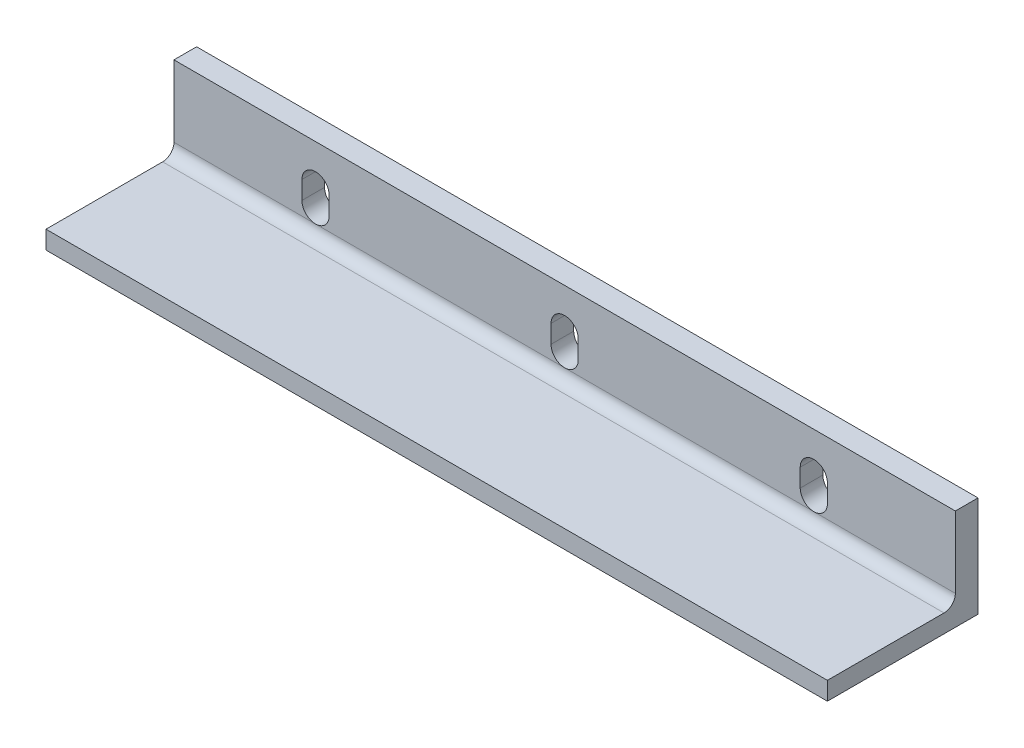
SolidWorks part; units mm, degrees
material "FR4_stuffedProtoboard"
ref_plane "Front Plane" through (0, 0, 0) normal (0, 0, 1) x (1, 0, 0)
ref_plane "Top Plane" through (0, 0, 0) normal (0, 1, 0) x (1, 0, 0)
ref_plane "Right Plane" through (0, 0, 0) normal (1, 0, 0) x (0, 0, -1)
sketch "Sketch1" plane through (0, 0, 0) normal (0, 1, 0) x (1, 0, 0)
  line L1 (-34.5, -6.65) -> (34.5, -6.65)
  line L2 (-34.5, -6.65) -> (-34.5, 6.65)
  line L3 (-34.5, 6.65) -> (34.5, 6.65)
  line L4 (34.5, -6.65) -> (34.5, 6.65)
  line L5 (-34.5, -6.65) -> (34.5, 6.65) construction
  line L6 (-34.5, 6.65) -> (34.5, -6.65) construction
  point P0 (0, 0)
  dimension "D1" = 13.3
  dimension "D2" = 69
extrude "Boss-Extrude1" add sketch "Sketch1" along normal blind 1.6
sketch "Sketch2" plane through (0, 1.6, 0) normal (0, 1, 0) x (1, 0, 0)
  line L0 (34.5, -6.65) -> (34.5, 6.65) construction
  line L1 (-34.5, 6.65) -> (34.5, 6.65)
  line L2 (-34.5, 6.65) -> (-34.5, 4.65)
  line L3 (-34.5, 4.65) -> (34.5, 4.65)
  line L4 (34.5, 6.65) -> (34.5, 4.65)
  dimension "D1" = 2
extrude "Boss-Extrude2" add sketch "Sketch2" along normal blind 7.3
fillet "Fillet1" radius 1 1 edges at (0, 1.6, -4.65)
sketch "Sketch3" plane through (0, 0, -6.65) normal (0, 0, 1) x (1, 0, 0)
  line L0 (0, 0) -> (0, 4.6) construction
  line L1 (22, 4.6) -> (-22, 4.6) construction
  point P6 (0, 4.6)
  dimension "D1" = 4.6
  dimension "D2" = 44
hole_wizard "M2 Clearance Slot1" positions "Sketch7" profile "Sketch8" size "M2" standard "ANSI Metric" slot yes end condition through all
sketch "Sketch7" plane through (0, 0, -4.65) normal (0, 0, 1) x (1, 0, 0)
  line L0 (-22, 2.6) -> (-22, 6.6) construction
  point P14 (-22, 4.6)
  point P19 (0, 4.6)
  point P22 (22, 4.6)
  dimension "D1" = 4
sketch "Sketch8" plane through (-22, 4.6, -4.65) normal (1, 0, 0) x (0, -1, 0)
  line L0 (0, 0) -> (0, 2)
  line L1 (0, 2) -> (1.2, 2)
  line L2 (1.2, 2) -> (1.2, 0)
  line L5 (1.2, 0) -> (0, 0)
  line L11 (0, -6.35) -> (0, 107.95) construction
  dimension "Thru Hole Dia." = 2.4
  dimension "Thru Hole Depth" = 2
